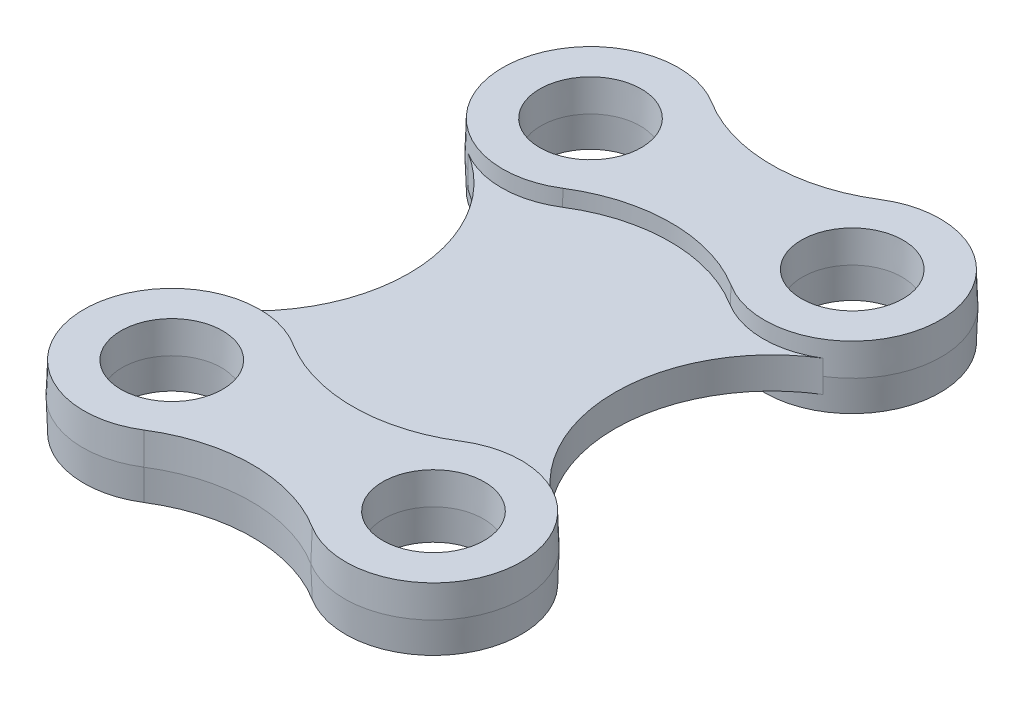
SolidWorks part; units mm, degrees
note: The reader was unsure of these and kept them because the rebuilt part matched: shared geometry of "Sketch1<4>".
ref_plane "Front Plane" through (0, 0, 0) normal (0, 0, 1) x (1, 0, 0)
ref_plane "Top Plane" through (0, 0, 0) normal (0, 1, 0) x (1, 0, 0)
ref_plane "Right Plane" through (0, 0, 0) normal (1, 0, 0) x (0, 0, -1)
sketch "Sketch1" plane through (0, 0, 0) normal (0, 1, 0) x (1, 0, 0)
  line L0 (0, 0) -> (0, -50000) construction
  line L1 (0, 0) -> (-50000, 0) construction
  circle A0 centre (25, -40) radius 9.5
  arc A1 (15.9574, -54.3956) -> (15.9574, -25.6044) centre (25, -40) ccw
  circle A2 centre (-25, -40) radius 9.5
  arc A3 (-15.9574, -54.3956) -> (-15.9574, -25.6044) centre (-25, -40) cw
  arc A4 (-15.9574, -54.3956) -> (15.9574, -54.3956) centre (0, -79.7995) cw
  arc A5 (-15.9574, -25.6044) -> (15.9574, -25.6044) centre (0, -0.2005) ccw
  arc A6 (-15.9574, 25.6044) -> (15.9574, 25.6044) centre (0, 0.2005) cw
  arc A7 (-15.9574, 54.3956) -> (15.9574, 54.3956) centre (0, 79.7995) ccw
  arc A8 (-15.9574, 54.3956) -> (-15.9574, 25.6044) centre (-25, 40) ccw
  circle A9 centre (-25, 40) radius 9.5
  arc A10 (15.9574, 54.3956) -> (15.9574, 25.6044) centre (25, 40) cw
  circle A11 centre (25, 40) radius 9.5
  arc A12 (-33.9261, 25.5319) -> (-33.9261, -25.5319) centre (-49.6779, 0) cw
  arc A13 (33.9261, 25.5319) -> (33.9261, -25.5319) centre (49.6779, 0) ccw
  dimension "D1" = 19
  dimension "D2" = 34
  dimension "D5" = 30
  dimension "D6" = 30
  dimension "D7" = 30
  dimension "D8" = 30
  dimension "D3" = 50
  dimension "D4" = 40
extrude "Boss-Extrude2" add sketch "Sketch1" along normal mid plane 6 contours A13 A10 A6 A8 A12 A3 A5 A1
extrude "Boss-Extrude3" add sketch "Sketch1<4>" along normal mid plane 12 draft 2 contours A10 A7 A8 A6 A9 A11 | A5 A3 A4 A1 A0 A2
sketch "Sketch1<4>" plane through (0, 0, 0) normal (0, 1, 0) x (1, 0, 0) same geometry as "Sketch1"
